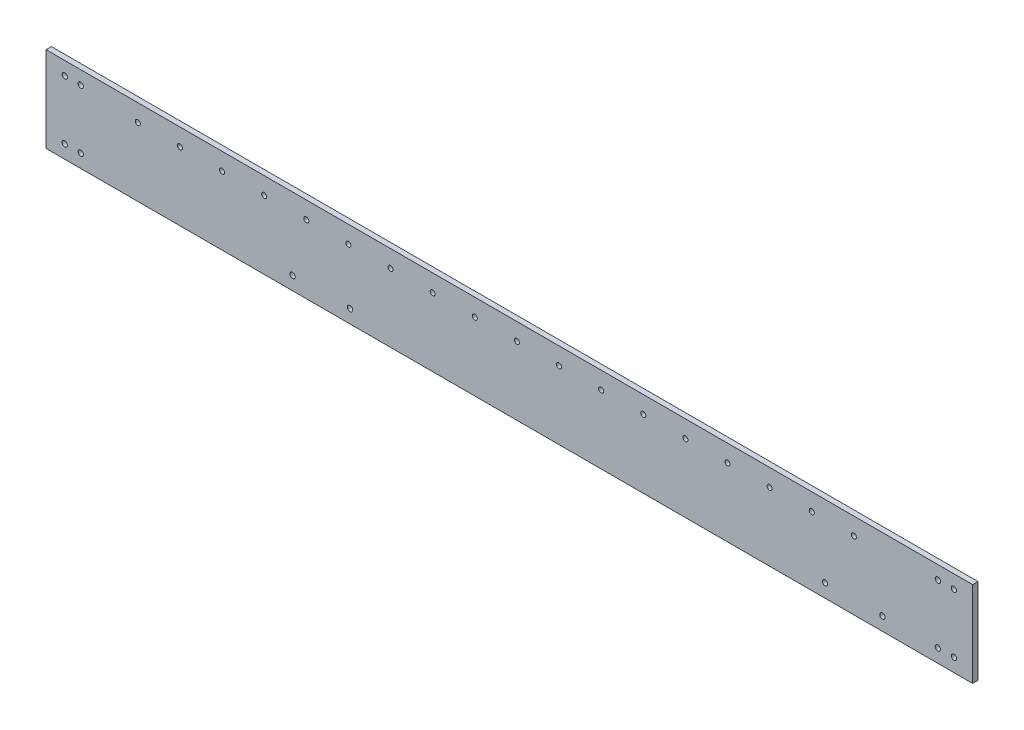
SolidWorks part; units mm, degrees
ref_plane "Front Plane" through (0, 0, 0) normal (0, 0, 1) x (1, 0, 0)
ref_plane "Top Plane" through (0, 0, 0) normal (0, 1, 0) x (1, 0, 0)
ref_plane "Right Plane" through (0, 0, 0) normal (1, 0, 0) x (0, 0, -1)
sketch "Sketch1" plane through (0, 0, 0) normal (1, 0, 0) x (0, 0, -1)
  line L0 (0, 0) -> (-3.175, 0)
  line L3 (-3.175, 0) -> (-3.175, 50.8)
  line L4 (-3.175, 50.8) -> (0, 50.8)
  line L5 (0, 50.8) -> (0, 0)
  dimension "LHeight" = 50.8
  dimension "LMaterialThickness" = 3.175
extrude "Boss-Extrude1" add sketch "Sketch1" along normal blind 550
sketch "SideHoles-Sketch4" plane through (0, 0, 3.175) normal (0, 0, 1) x (1, 0, 0)
  line L1 (550, 50.8) -> (550, 0) construction
  line L2 (0, 50.8) -> (0, 0) construction
  line L3 (550, 50.8) -> (0, 50.8) construction
  line L4 (550, 0) -> (0, 0) construction
  line L5 (550, 50.8) -> (0, 50.8) construction
  line L6 (0, 50.8) -> (0, 0) construction
  line L7 (550, 50.8) -> (550, 0) construction
  circle A1 centre (11.1125, 42.8625) radius 1.5875
  circle A3 centre (529.3625, 42.8625) radius 1.5875
  circle A4 centre (20.6375, 42.8625) radius 1.5875
  circle A5 centre (538.8875, 42.8625) radius 1.5875
  circle A6 centre (11.1125, 7.9375) radius 1.5875
  circle A7 centre (20.6375, 7.9375) radius 1.5875
  circle A8 centre (529.3625, 7.9375) radius 1.5875
  circle A9 centre (538.8875, 7.9375) radius 1.5875
  circle A10 centre (54.5, 40.575) radius 1.5
  circle A11 centre (79.5, 40.575) radius 1.5
  circle A12 centre (104.5, 40.575) radius 1.5
  circle A13 centre (129.5, 40.575) radius 1.5
  circle A14 centre (154.5, 40.575) radius 1.5
  circle A15 centre (179.5, 40.575) radius 1.5
  circle A16 centre (204.5, 40.575) radius 1.5
  circle A17 centre (229.5, 40.575) radius 1.5
  circle A18 centre (254.5, 40.575) radius 1.5
  circle A19 centre (279.5, 40.575) radius 1.5
  circle A20 centre (304.5, 40.575) radius 1.5
  circle A21 centre (329.5, 40.575) radius 1.5
  circle A22 centre (354.5, 40.575) radius 1.5
  circle A23 centre (379.5, 40.575) radius 1.5
  circle A24 centre (496.4875, 7.9375) radius 1.5875
  circle A26 centre (180.4875, 7.9375) radius 1.5875
  circle A29 centre (404.5, 40.575) radius 1.5
  circle A30 centre (429.5, 40.575) radius 1.5
  circle A31 centre (454.5, 40.575) radius 1.5
  circle A32 centre (479.5, 40.575) radius 1.5
  circle A34 centre (146.3625, 7.9375) radius 1.5875
  circle A36 centre (462.3625, 7.9375) radius 1.5875
  dimension "D2" = 3.175
  dimension "D10" = 3
  dimension "D14" = 3.175
  dimension "D4" = 7.9375
  dimension "D3" = 11.1125
  dimension "D5" = 20.6375
  dimension "D1" = 11.1125
  dimension "D6" = 20.6375
  dimension "D7" = 7.9375
  dimension "D9" = 10.225
  dimension "D8" = 54.5
  dimension "D12" = 25
  dimension "D15" = 7.9375
  dimension "D17" = 53.5125
  dimension "D18" = 316
  dimension "D13" = 34.125
  dimension "D16" = 34.125
  dimension "D11" = 18
extrude "SideHoles-Cut-Extrude3" cut sketch "SideHoles-Sketch4" against normal through all
equation "\"MidLeftOrRightSideRailHeight\"= 2.0in"
equation "\"RailThickness\"= .125in'Spec"
equation "\"SideRailHoleY1FromEdge\"= \"HoleOffsetFromEdge\""
equation "\"SideRailHoleX1FromSide\"= \"HoleOffsetFromSide\""
equation "\"MidSideRailLength\"= \"SideRailLength\""
equation "\"VSWidth\"= 1.25in'Spec"
equation "\"HoleOffsetFromEdge\"= \"RailThickness\" * 2.5"
equation "\"HoleOffsetFromSide\"= \"RailThickness\" * 3.5"
equation "\"SideRailHoleX2FromSide\"= \"VSWidth\" - \"HoleOffsetFromEdge\" - \"RailThickness\"'Equals 20.6375"
equation "\"FasteningHoleDiameter\"= .125in"
equation "\"StepperWidth\"= 42mm'Spec"
equation "\"D2@SideHoles-Sketch4\"=\"FasteningHoleDiameter\""
equation "\"LHeight@Sketch1\"=\"MidLeftOrRightSideRailHeight\""
equation "\"LMaterialThickness@Sketch1\"=\"RailThickness\""
equation "\"D1@Boss-Extrude1\"=\"MidSideRailLength\""
equation "\"D4@SideHoles-Sketch4\"=\"SideRailHoleY1FromEdge\""
equation "\"D3@SideHoles-Sketch4\"=\"SideRailHoleX1FromSide\" "
equation "\"D5@SideHoles-Sketch4\"=\"SideRailHoleX2FromSide\" "
equation "\"D1@SideHoles-Sketch4\"=\"SideRailHoleX1FromSide\" "
equation "\"D6@SideHoles-Sketch4\"=\"SideRailHoleX2FromSide\""
equation "\"LinearRailXMountHole\"= \"StepperWidth\" + \"LinearRailFirstHoleOffsetFromEdge\""
equation "\"D9@SideHoles-Sketch4\"=\"V6.3 GantryMiddleToToTopOfMidSideRail\""
equation "\"D8@SideHoles-Sketch4\"=\"LinearRailXMountHole\""
equation "\"LinearRailHoleDistance\"= 25mm'Spec"
equation "\"D12@SideHoles-Sketch4\"=\"LinearRailHoleDistance\""
equation "\"SideRailLength\"= 550mm"
equation "\"LinearRailFirstHoleOffsetFromEdge\"= 12.5mm'Spec"
equation "\"D7@SideHoles-Sketch4\"= \"MidRailRodStabilizerMountingHoleOffsetFromEdge\""
equation "\"DistanceFromBedFrontToFirstLeftStepperHole\"= \"LeadScrewNutPadSize\" + 10mm'Equals 34"
equation "\"BeltTensionerDepth\"= \"BeltTensionerBackWallThickness\" + \"BeltTensionerInnerDepth\"'Equals 23.4"
equation "\"20TGT2PulleyDiameter\"= 17.9mm'Spec"
equation "\"BeltTensionerSpaceBetweenPulleyAndWall\"= 1.5mm"
equation "\"BeltTensionerBackWallThickness\"= 4mm"
equation "\"BeltTensionerInnerDepth\"= \"20TGT2PulleyDiameter\" + \"BeltTensionerSpaceBetweenPulleyAndWall\""
equation "\"DistanceFromFrontSideToBedFront\"= \"RailThickness\" + \"BeltTensionerDepth\" + 10mm'Equals 36.575"
equation "\"DistanceBetweenFrontToBackStepperHoles\"= \"BedLength\" - \"DistanceFromBedFrontToFirstLeftStepperHole\"'Equals 316"
equation "\"BedLength\"= \"BedInnerSquareLength\" + \"BedLWidth\" * 2 + \"BedIncreasedByLength\"'Equals 350"
equation "\"BedThirdSize\"= 70mm"
equation "\"BedInnerSquareWidth\"= \"BedThirdSize\" * 3'Equals 210"
equation "\"BedLWidth\"= \"BedThirdSize\"'Equals 70"
equation "\"BedIncreasedByLength\"= 0mm"
equation "\"D14@SideHoles-Sketch4\"= \"FasteningHoleDiameter\""
equation "\"D15@SideHoles-Sketch4\"= \"HoleOffsetFromEdge\""
equation "\"BedInnerSquareLength\"= \"BedInnerSquareWidth\""
equation "\"GABMidWallHeight\"= 28mm'Must equal 28 or changes alignment"
equation "\"20TGT2PulleyWidth\"= 8.7mm'The STL of the Pulley in the diagram is a bit larger"
equation "\"GABMidShortRiserHeight\"= \"GABMidWallHeight\" / 2 - \"20TGT2PulleyWidth\"'Equals 5.3"
equation "\"GABUpperHeight\"= 6mm"
equation "\"GABLowerHeight\"= 3mm"
equation "\"GABRiserBossOffset\"= 0.8mm'Aligns Pulleys"
equation "\"GABHeight\"= \"GABLowerHeight\" + \"GABMidWallHeight\" + \"GABUpperHeight\""
equation "\"StepperShaftLength\"= 24mm'Pulley will be attached to the end"
equation "\"V6.1 FromGantryPulleyToGantryMiddle\"= \"GABHeight\" / 2 - \"GABMidShortRiserHeight\" - \"GABLowerHeight\" + \"GABRiserBossOffset\" / 2"
equation "\"V6.2 GantryMiddleToTopOfMidBackRail\"= \"StepperShaftLength\" - \"V6.1 FromGantryPulleyToGantryMiddle\""
equation "\"V6.3 GantryMiddleToToTopOfMidSideRail\"= \"V6.2 GantryMiddleToTopOfMidBackRail\" - \"RailThickness\""
equation "\"DistanceFromFrontSideToFirstLeftStabilizerMountingHole\"= \"DistanceFromFrontSideToFirstLeftStepperHole\" - \"DistanceFromStepperHoleToRodStabilizerMountingHole\"'Equals 53.5125"
equation "\"DistanceFromFrontSideToFirstLeftStepperHole\"= \"DistanceFromFrontSideToBedFront\" + \"DistanceFromBedFrontToFirstLeftStepperHole\"'Equals 70.575"
equation "\"LeadScrewNutMountingHoleFlangeDiameter\"= 22mm'Spec"
equation "\"LeadScrewNutPadSize\"= \"LeadScrewNutMountingHoleFlangeDiameter\" + 2mm'Equals 24"
equation "\"D17@SideHoles-Sketch4\"=\"DistanceFromFrontSideToFirstLeftStabilizerMountingHole\""
equation "\"D18@SideHoles-Sketch4\"=\"DistanceBetweenFrontToBackStepperHoles\""
equation "\"MidRailRodStabilizerMountingHoleOffsetFromEdge\"= \"HoleOffsetFromEdge\""
equation "\"RodStabilizerLength\"= 50mm"
equation "\"DistanceFromStepperHoleToRodStabilizerMountingHole\"= \"RodStabilizerLength\" / 2 - \"HoleOffsetFromEdge\"'Equals 17.0625"
equation "\"D13@SideHoles-Sketch4\"=\"RodStabilizerLength\" - \"HoleOffsetFromEdge\" * 2"
equation "\"D16@SideHoles-Sketch4\"=\"RodStabilizerLength\" - \"HoleOffsetFromEdge\" *2"
